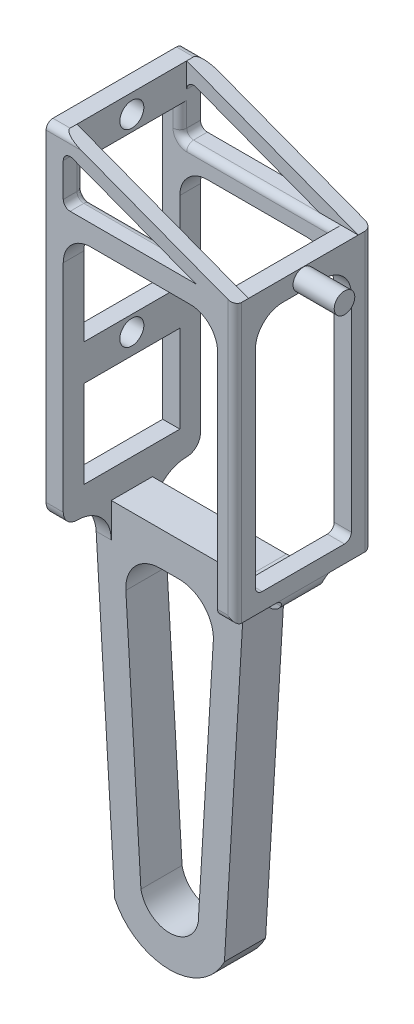
SolidWorks part; units mm, degrees
ref_plane "前视基准面" through (0, 0, 0) normal (0, 0, 1) x (1, 0, 0)
ref_plane "上视基准面" through (0, 0, 0) normal (0, 1, 0) x (1, 0, 0)
ref_plane "右视基准面" through (0, 0, 0) normal (1, 0, 0) x (0, 0, -1)
sketch "草图1" plane through (0, 0, 0) normal (0, 0, 1) x (1, 0, 0)
  line L0 (0, 0) -> (0, -100) construction
  line L1 (-11, -45) -> (11, -45)
  line L2 (-8, -95) -> (8, -95) construction
  line L3 (-8, -95) -> (-11, -45)
  line L4 (8, -95) -> (11, -45)
  arc A0 (-8, -95) -> (8, -95) centre (0, -91.1) ccw
  point P3 (0, -45)
  point P4 (0, -95)
  point P7 (0, -45)
  point P11 (0, -95)
  dimension "D1" = 100
  dimension "D2" = 55
  dimension "D3" = 22
  dimension "D4" = 5
  dimension "D5" = 16
extrude "凸台-拉伸1" add sketch "草图1" along normal mid plane 6
sketch "草图2" plane through (0, -45, 0) normal (0, 1, 0) x (1, 0, 0)
  line L0 (-12.1, 0) -> (12.1, 0) construction
  line L1 (-8.5, 10) -> (-11, 10)
  line L2 (-8.5, 10) -> (-8.5, -10)
  line L3 (-8.5, -10) -> (-11, -10)
  line L4 (-11, 10) -> (-11, -10)
  line L5 (-8.5, 10) -> (-11, -10) construction
  line L6 (-8.5, -10) -> (-11, 10) construction
  line L7 (-11, -3) -> (-11, 3) construction
  point P4 (-9.75, 0)
  dimension "D1" = 20
  dimension "D2" = 2.5
  dimension "D3" = 0
extrude "凸台-拉伸2" add sketch "草图2" along normal blind 22
sketch "草图3" plane through (0, -23, 0) normal (0, 1, 0) x (1, 0, 0)
  line L0 (-8.5, -10) -> (-8.5, 10) construction
  line L1 (-8.5, 10) -> (-11, 10)
  line L2 (-8.5, 10) -> (-8.5, 7)
  line L3 (-8.5, 7) -> (-11, 7)
  line L4 (-11, 10) -> (-11, 7)
  line L5 (-8.5, 10) -> (-11, 7) construction
  line L6 (-8.5, 7) -> (-11, 10) construction
  line L7 (-11, 10) -> (-11, -10) construction
  line L8 (-8.5, 10) -> (-11, 10) construction
  line L9 (-8.5, -10) -> (-11, -10)
  line L10 (-8.5, -10) -> (-8.5, -7)
  line L11 (-8.5, -7) -> (-11, -7)
  line L12 (-11, -10) -> (-11, -7)
  line L13 (-8.5, -10) -> (-11, -7) construction
  line L14 (-8.5, -7) -> (-11, -10) construction
  point P4 (-9.75, 8.5)
  point P14 (-9.75, -8.5)
  dimension "D1" = 3
  dimension "D2" = 3
extrude "凸台-拉伸3" add sketch "草图3" along normal blind 28
sketch "草图4" plane through (0, 0, -7) normal (0, 0, 1) x (1, 0, 0)
  line L0 (-8.5, 5) -> (-8.5, -23) construction
  line L1 (-11, 5) -> (-8.5, 5)
  line L2 (-11, 5) -> (-11, 0)
  line L3 (-11, 0) -> (-8.5, 0)
  line L4 (-8.5, 5) -> (-8.5, 0)
  line L5 (-11, 5) -> (-8.5, 0) construction
  line L6 (-11, 0) -> (-8.5, 5) construction
  point P4 (-9.75, 2.5)
  dimension "D1" = 5
extrude "凸台-拉伸4" add sketch "草图4" along normal up to next
sketch "草图5" plane through (-11, 0, 0) normal (-1, 0, 0) x (0, 0, 1)
  line L0 (0, -12.1) -> (0, 12.1) construction
  line L2 (-7, -23) -> (7, -23) construction
  circle A0 centre (0, -25.25) radius 1.75
  circle A1 centre (0, 2.25) radius 1.75
  dimension "D1" = 3.5
  dimension "D2" = 3.5
  dimension "D3" = 27.5
  dimension "D4" = 2.25
extrude "切除-拉伸1" cut sketch "草图5" against normal up to next
sketch "草图13" plane through (-8.5, 0, 0) normal (1, 0, 0) x (0, 0, -1)
  line L0 (-10, 5) -> (-10, -45) construction
  line L1 (-10, -4.5) -> (-7, -4.5)
  line L2 (-10, -4.5) -> (-10, -7.5)
  line L3 (-10, -7.5) -> (-7, -7.5)
  line L4 (-7, -4.5) -> (-7, -7.5)
  line L5 (-10, -4.5) -> (-7, -7.5) construction
  line L6 (-10, -7.5) -> (-7, -4.5) construction
  line L7 (-7, 0) -> (-7, -23) construction
  line L8 (7, 0) -> (7, -23) construction
  line L9 (7, -4.5) -> (10, -4.5)
  line L10 (7, -4.5) -> (7, -7.5)
  line L11 (7, -7.5) -> (10, -7.5)
  line L12 (10, -4.5) -> (10, -7.5)
  line L13 (7, -4.5) -> (10, -7.5) construction
  line L14 (7, -7.5) -> (10, -4.5) construction
  line L15 (10, 5) -> (10, -45) construction
  line L16 (-10, 5) -> (10, 5) construction
  point P4 (-8.5, -6)
  point P14 (8.5, -6)
  dimension "D1" = 11
  dimension "D2" = 3
  dimension "D3" = 3
extrude "凸台-拉伸9" add sketch "草图13" along normal blind 25
sketch "草图14" plane through (0, 0, -7) normal (0, 0, 1) x (1, 0, 0)
  line L0 (16.5, -4.5) -> (-8.5, -4.5) construction
  line L1 (16.5, -4.5) -> (14, -4.5)
  line L2 (16.5, -4.5) -> (16.5, -7.5)
  line L3 (16.5, -7.5) -> (14, -7.5)
  line L4 (14, -4.5) -> (14, -7.5)
  line L5 (16.5, -4.5) -> (14, -7.5) construction
  line L6 (16.5, -7.5) -> (14, -4.5) construction
  line L7 (16.5, -4.5) -> (16.5, -7.5) construction
  line L8 (16.5, -7.5) -> (-8.5, -7.5) construction
  point P4 (15.25, -6)
  dimension "D1" = 2.5
extrude "凸台-拉伸10" add sketch "草图14" along normal up to surface (14 mm away) up to face at (-2.875, -8.75, 7)
sketch "草图11" plane through (16.5, 0, 0) normal (1, 0, 0) x (0, 0, -1)
  circle A0 centre (0, -6.05) radius 1.5
  circle A1 centre (0, -6.05) radius 2 construction
  dimension "D1" = 3
extrude "凸台-拉伸8" add sketch "草图11" along normal blind 6
fillet "圆角1" radius 2 2 edges at (-9.75, -45, -10) (-9.75, -45, 10)
sketch "草图15" plane through (0, 0, 3) normal (0, 0, 1) x (1, 0, 0)
  line L0 (-6.6928, -50) -> (6.6928, -50)
  line L1 (6.6928, -50) -> (4.1773, -91.9246)
  line L3 (-4.1773, -91.9246) -> (-6.6928, -50)
  line L4 (-11, -45) -> (-8, -95) construction
  line L5 (8, -95) -> (11, -45) construction
  line L6 (11, -45) -> (-8.5, -45) construction
  line L7 (8, -95) -> (11, -45) construction
  arc A2 (-4.1773, -91.9246) -> (4.1773, -91.9246) centre (0, -91.1) ccw
  arc A3 (-8, -95) -> (8, -95) centre (0, -91.1) ccw construction
  dimension "D1" = 5
  dimension "D3" = 4
  dimension "D4" = 4
extrude "切除-拉伸2" cut sketch "草图15" against normal up to next
fillet "圆角5" radius 5 4 edges at (-6.6928, -50, 0) (6.6928, -50, 0) (-9.75, -45, -3) (-9.75, -45, 3)
ref_plane "基准面1" through (0, 0, 10) normal (0, 0, 1) x (1, 0, 0)
sketch "草图16" plane through (0, 0, 10) normal (0, 0, 1) x (1, 0, 0)
  line L0 (-8.5, 5) -> (16.5, -4.5)
  line L1 (16.5, -4.5) -> (10.8697, -4.5)
  line L2 (10.8697, -4.5) -> (-8.5, 2.8605)
  line L3 (-8.5, 5) -> (-8.5, -4.5) construction
  line L4 (-8.5, 2.8605) -> (-8.5, 5)
  dimension "D1" = 2
extrude "凸台-拉伸11" add sketch "草图16" against normal blind 2
mirror "镜向1" about plane through (0, 0, 0) normal (0, 0, 1) of "凸台-拉伸11"
sketch "草图17" plane through (0, -7.5, 0) normal (0, -1, 0) x (1, 0, 0)
  line L0 (16.5, -1.5) -> (16.5, 1.5) construction
  line L1 (16.5, 7) -> (14, 7)
  line L2 (16.5, 7) -> (16.5, 10)
  line L3 (16.5, 10) -> (14, 10)
  line L4 (14, 7) -> (14, 10)
  line L5 (16.5, 7) -> (14, 10) construction
  line L6 (16.5, 10) -> (14, 7) construction
  line L7 (16.5, -0.3841) -> (16.5, -10) construction
  line L8 (14, 7) -> (14, -7) construction
  line L11 (16.5, 10) -> (-8.5, 10) construction
  line L12 (14, 7) -> (-8.5, 7) construction
  line L13 (16.5, -10) -> (-8.5, -10) construction
  line L14 (14, -7) -> (16.5, -7)
  line L15 (14, -7) -> (14, -10)
  line L16 (14, -10) -> (16.5, -10)
  line L17 (16.5, -7) -> (16.5, -10)
  line L18 (14, -7) -> (16.5, -10) construction
  line L19 (14, -10) -> (16.5, -7) construction
  point P4 (15.25, 8.5)
  point P19 (15.25, -8.5)
extrude "凸台-拉伸12" add sketch "草图17" along normal up to surface (37.5 mm away) up to face at (1.25, -45, 0)
sketch "草图18" plane through (0, 0, -7) normal (0, 0, 1) x (1, 0, 0)
  line L0 (16.5, -45) -> (16.5, -7.5) construction
  line L1 (14, -45) -> (16.5, -45)
  line L2 (14, -45) -> (14, -42.5)
  line L3 (14, -42.5) -> (16.5, -42.5)
  line L4 (16.5, -45) -> (16.5, -42.5)
  line L5 (14, -45) -> (16.5, -42.5) construction
  line L6 (14, -42.5) -> (16.5, -45) construction
  point P4 (15.25, -43.75)
  dimension "D1" = 2.5
extrude "凸台-拉伸13" add sketch "草图18" along normal up to next
sketch "草图19" plane through (59, -45, 0) normal (0, 1, 0) x (0, 0, 1)
  line L1 (-3, -42.5) -> (3, -42.5)
  line L2 (-3, -42.5) -> (-3, -45)
  line L3 (-3, -45) -> (3, -45)
  line L4 (3, -42.5) -> (3, -45)
  line L5 (-3, -42.5) -> (3, -45) construction
  line L6 (-3, -45) -> (3, -42.5) construction
  line L8 (3, -48) -> (3, -67.5) construction
  line L9 (-3, -48) -> (-3, -67.5) construction
  line L10 (10, -45) -> (-10, -45) construction
  line L11 (-10, -42.5) -> (10, -42.5) construction
  point P4 (0, -43.75)
sketch "草图20" plane through (-11, 0, 0) normal (-1, 0, 0) x (0, 0, 1)
  line L0 (-7, 0) -> (-7, -23) construction
  line L1 (-7, -28.25) -> (7, -28.25)
  line L2 (-7, -28.25) -> (-7, -41)
  line L3 (-7, -41) -> (7, -41)
  line L4 (7, -28.25) -> (7, -41)
  line L5 (-7, -28.25) -> (7, -41) construction
  line L6 (-7, -41) -> (7, -28.25) construction
  line L7 (7, 0) -> (7, -23) construction
  line L8 (8, -45) -> (-8, -45) construction
  circle A0 centre (0, -25.25) radius 1.75 construction
  point P4 (0, -34.625)
  dimension "D1" = 4
  dimension "D2" = 3
extrude "切除-拉伸3" cut sketch "草图20" against normal up to next
extrude "凸台-拉伸15" add sketch "草图19" against normal blind 2
sketch "草图25" plane through (14, 0, 0) normal (-1, 0, 0) x (0, 0, 1)
  line L1 (-3, -45) -> (3, -45)
  line L2 (-3, -45) -> (-3, -47)
  line L3 (-3, -47) -> (3, -47)
  line L4 (3, -45) -> (3, -47)
  line L5 (-3, -45) -> (3, -47) construction
  line L6 (-3, -47) -> (3, -45) construction
  point P4 (0, -46)
extrude "凸台-拉伸16" add sketch "草图25" along normal up to next
fillet "圆角10" radius 2 2 edges at (16.5, -47, 0) (10.88, -47, 0)
ref_plane "基准面2" through (0, -100, 0) normal (0, -1, 0) x (-1, 0, 0)
fillet "圆角11" radius 4 4 edges at (-8.5, -7.5, -8.5) (15.25, -7.5, -7) (15.25, -7.5, 7) (-8.5, -7.5, 8.5)
fillet "圆角12" radius 4 2 edges at (14, -7.5, -8.5) (14, -7.5, 8.5)
fillet "圆角8" radius 1 18 edges at (-8.5, 2.8605, -9) (-8.5, -4.5, -8.5) (-8.5, -4.5, 8.5) (-8.5, 2.8605, 9) (16.5, -24.75, -10) (16.5, -24.75, 10) (2.75, -4.5, 7) (2.75, -4.5, -7) (-8.5, -2.25, 7) (-8.5, -2.25, -7) (15.25, -42.5, 7) (15.25, -42.5, -7) (15.25, -45, -10) (15.25, -45, 10) (-9.75, 5, 10) (-9.75, 5, -10) (15.25, -45, -3) (15.25, -45, 3)
fillet "圆角13" radius 3 1 edges at (14, -45, 0)
